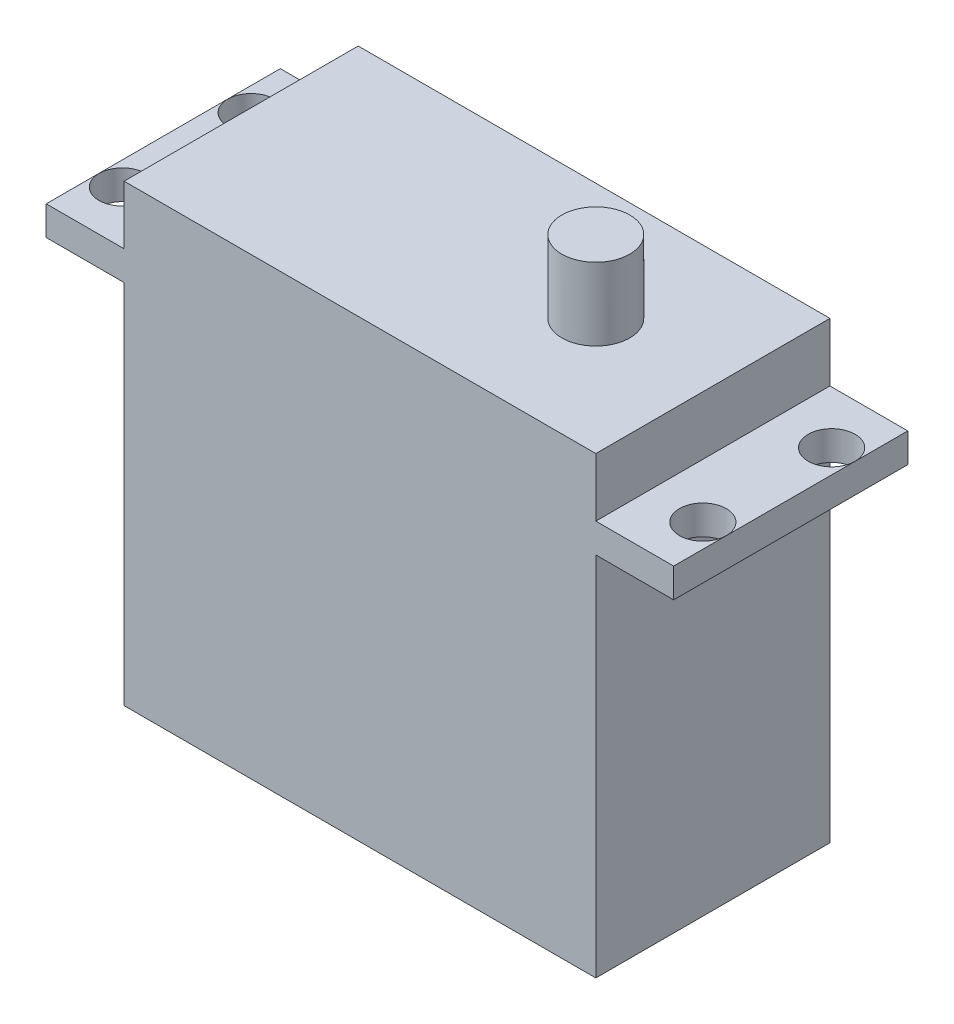
SolidWorks part; units mm, degrees
ref_plane "Front Plane" through (0, 0, 0) normal (0, 0, 1) x (1, 0, 0)
ref_plane "Top Plane" through (0, 0, 0) normal (0, 1, 0) x (1, 0, 0)
ref_plane "Right Plane" through (0, 0, 0) normal (1, 0, 0) x (0, 0, -1)
sketch "Sketch1" plane through (0, 0, 0) normal (0, 1, 0) x (1, 0, 0)
  line L1 (-20.15, -10) -> (20.15, -10)
  line L2 (-20.15, -10) -> (-20.15, 10)
  line L3 (-20.15, 10) -> (20.15, 10)
  line L4 (20.15, -10) -> (20.15, 10)
  line L5 (-20.15, -10) -> (20.15, 10) construction
  line L6 (-20.15, 10) -> (20.15, -10) construction
  point P0 (0, 0)
  dimension "D1" = 20
  dimension "D2" = 40.3
extrude "Boss-Extrude1" add sketch "Sketch1" along normal blind 38.8
sketch "Sketch2" plane through (0, 38.8, 0) normal (0, 1, 0) x (1, 0, 0)
  line L0 (20.15, 0) -> (10.15, 0) construction
  line L1 (20.15, -10) -> (20.15, 10) construction
  circle A0 centre (10.15, 0) radius 2.9
  dimension "D2" = 5.8
  dimension "D1" = 10
extrude "Boss-Extrude2" add sketch "Sketch2" along normal blind 6.2
sketch "Sketch3" plane through (0, 38.8, 0) normal (0, 1, 0) x (1, 0, 0)
  line L0 (-26.8, 0) -> (26.8, 0) construction
  line L1 (-20.15, 10) -> (-26.8, 10)
  line L2 (-20.15, -10) -> (-26.8, -10)
  line L3 (-26.8, -10) -> (-26.8, 10)
  line L4 (20.15, 10) -> (26.8, 10)
  line L5 (26.8, 10) -> (26.8, -10)
  line L6 (26.8, -10) -> (20.15, -10)
  line L7 (-20.15, 10) -> (-20.15, -10)
  line L8 (20.15, 10) -> (20.15, -10)
  line L9 (-26.8, 3.75) -> (-26.8, -3.75)
  line L10 (0, -10) -> (0, 10) construction
  line L11 (-20.15, -10) -> (20.15, -10) construction
  line L12 (20.15, 10) -> (-20.15, 10) construction
  circle A0 centre (-24.7944, 5.5) radius 2
  circle A1 centre (-24.7944, -5.5) radius 2
  circle A2 centre (24.7944, -5.5) radius 2
  circle A3 centre (24.7944, 5.5) radius 2
  point P4 (0, 0)
  point P20 (-26.8, 0)
  line M4 (20.15, -10) -> (20.15, 10)
  line M6 (-20.15, 10) -> (-20.15, -10)
  dimension "D4" = 4
  dimension "D5" = 4.5
  dimension "D1" = 53.6
  dimension "D2" = 6.65
  dimension "D3" = 7.5
extrude "Boss-Extrude3" add sketch "Sketch3" against normal blind 2.5 from offset 5 contours L3 L2 L1 A0 A1 M6 | L6 L5 L4 A2 A3 M4 region at (-23.1676, 38.8, 0) region at (23.1676, 38.8, 0) offset against normal yes
